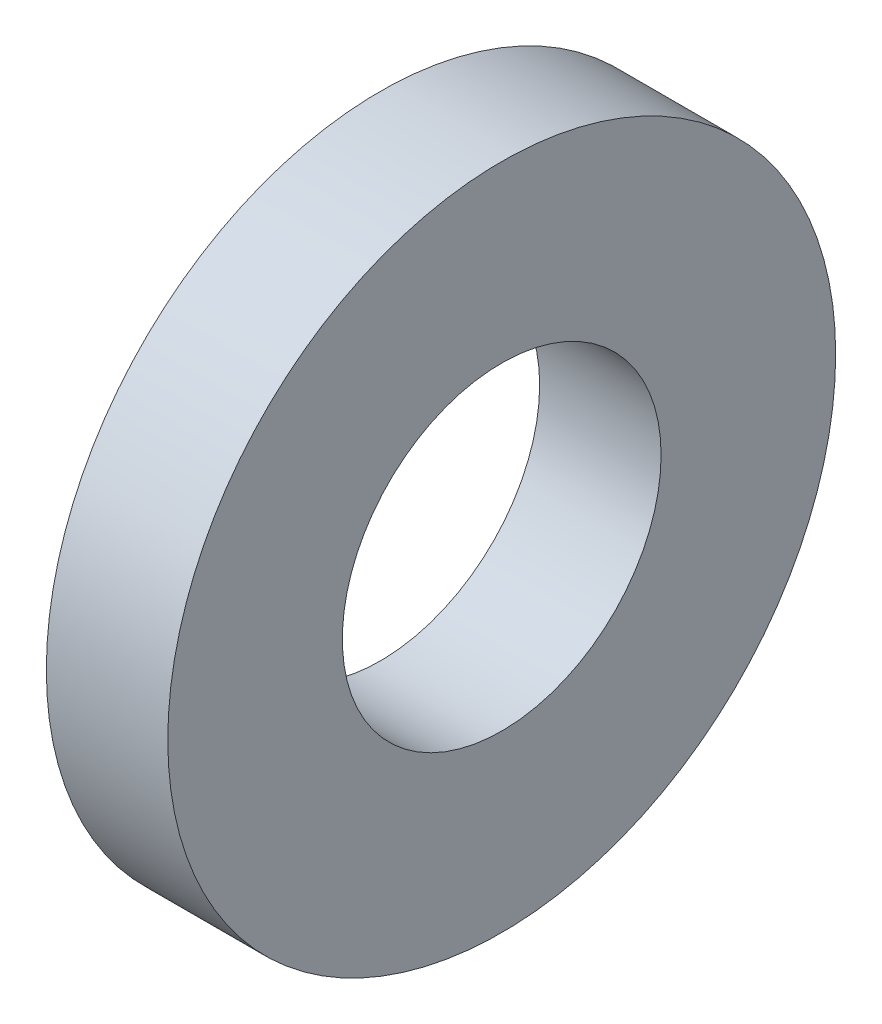
SolidWorks part; units mm, degrees
ref_plane "Plane1" through (0, 0, 0) normal (0, 0, 1) x (1, 0, 0)
ref_plane "Plane2" through (0, 0, 0) normal (0, 1, 0) x (1, 0, 0)
ref_plane "Plane3" through (0, 0, 0) normal (1, 0, 0) x (0, 0, -1)
sketch "Sketch1" plane through (0, 0, 0) normal (1, 0, 0) x (0, 0, -1)
  circle A0 centre (0, 0) radius 10.5
  circle A1 centre (0, 0) radius 22
  dimension "InsideDia" = 21
  dimension "OutsideDia" = 44
extrude "Base-Extrude" add sketch "Sketch1" along normal blind 8
